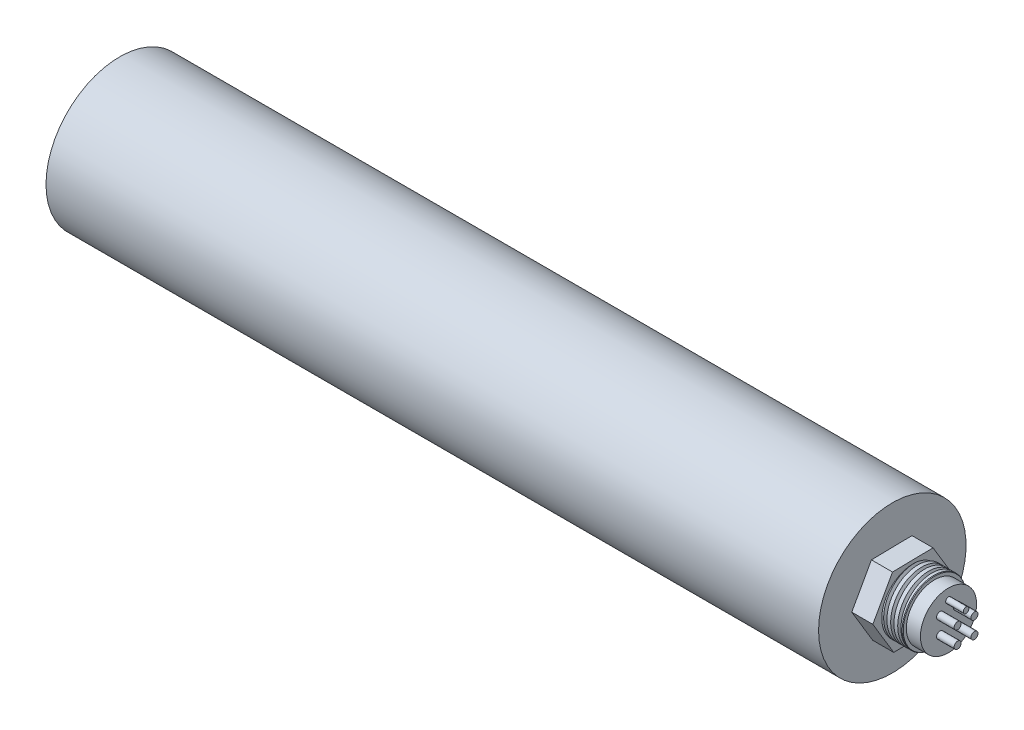
SolidWorks part; units mm, degrees
ref_plane "Front Plane" through (0, 0, 0) normal (0, 0, 1) x (1, 0, 0)
ref_plane "Top Plane" through (0, 0, 0) normal (0, 1, 0) x (1, 0, 0)
ref_plane "Right Plane" through (0, 0, 0) normal (1, 0, 0) x (0, 0, -1)
sketch "Sketch3" plane through (0, 0, 0) normal (1, 0, 0) x (0, 0, -1)
  line L1 (14.6625, 0.2559) -> (7.1096, 12.826)
  line L2 (7.1096, 12.826) -> (-7.5529, 12.5701)
  line L3 (-7.5529, 12.5701) -> (-14.6625, -0.2559)
  line L4 (-14.6625, -0.2559) -> (-7.1096, -12.826)
  line L5 (-7.1096, -12.826) -> (7.5529, -12.5701)
  line L6 (7.5529, -12.5701) -> (14.6625, 0.2559)
  circle A0 centre (0, 0) radius 12.7 construction
extrude "Boss-Extrude1" add sketch "Sketch3" along normal blind 7.62
sketch "Sketch4" plane through (7.62, 0, 0) normal (1, 0, 0) x (0, 0, -1)
  circle A0 centre (0, 0) radius 10.16
extrude "Boss-Extrude2" add sketch "Sketch4" along normal blind 12.7
sketch "Sketch5" plane through (7.62, 0, 0) normal (1, 0, 0) x (0, 0, -1)
  circle A0 centre (0, 0) radius 10.16
extrude "Extrude-Thin1" add sketch "Sketch5" along normal blind 7.62 thin
chamfer "Chamfer2" distance 0.254 angle 30 1 edges at (15.24, 0, -11.43)
sketch "Sketch6" plane through (15.24, 0, 0) normal (1, 0, 0) x (0, 0, -1)
  circle A0 centre (0, 0) radius 11.43
curve "Helix/Spiral1" pitch 2.54 height 7.62 turns 3
sketch "Sketch9" plane through (0, 0, 0) normal (0, 1, 0) x (1, 0, 0)
  line L1 (15.24, 10.414) -> (16.1199, 11.938)
  line L2 (16.1199, 11.938) -> (14.3601, 11.938)
  line L3 (14.3601, 11.938) -> (15.24, 10.414)
  circle A0 centre (15.24, 11.43) radius 0.508 construction
  spline S0 degree 3 poles (15.24, 11.43) (15.1874, 11.43) (15.0811, 10.8349) (14.9225, 8.2926) (14.7637, 4.4879) (14.605, 0) (14.4462, -4.4879) (14.2875, -8.2926) (14.1287, -10.8349) (13.97, -11.7276) (13.8112, -10.8349) (13.6525, -8.2926) (13.4937, -4.4879) (13.335, 0) (13.1762, 4.4879) (13.0175, 8.2926) (12.8587, 10.8349) (12.7, 11.7276) (12.5412, 10.8349) (12.3825, 8.2926) (12.2237, 4.4879) (12.065, 0) (11.9062, -4.4879) (11.7475, -8.2926) (11.5887, -10.8349) (11.43, -11.7276) (11.2712, -10.8349) (11.1125, -8.2926) (10.9537, -4.4879) (10.795, 0) (10.6363, 4.4879) (10.4775, 8.2926) (10.3188, 10.8349) (10.16, 11.7276) (10.0013, 10.8349) (9.8425, 8.2926) (9.6838, 4.4879) (9.525, 0) (9.3663, -4.4879) (9.2075, -8.2926) (9.0488, -10.8349) (8.89, -11.7276) (8.7313, -10.8349) (8.5725, -8.2926) (8.4138, -4.4879) (8.255, 0) (8.0963, 4.4879) (7.9375, 8.2926) (7.7789, 10.8349) (7.6726, 11.43) (7.62, 11.43) knots 0 0 0 0 0.020833 0.041667 0.0625 0.083333 0.104167 0.125 0.145833 0.166667 0.1875 0.208333 0.229167 0.25 0.270833 0.291667 0.3125 0.333333 0.354167 0.375 0.395833 0.416667 0.4375 0.458333 0.479167 0.5 0.520833 0.541667 0.5625 0.583333 0.604167 0.625 0.645833 0.666667 0.6875 0.708333 0.729167 0.75 0.770833 0.791667 0.8125 0.833333 0.854167 0.875 0.895833 0.916667 0.9375 0.958333 0.979167 1 1 1 1 construction
sweep "Cut-Sweep4" cut profiles "Sketch9" path "Helix/Spiral1"
sketch "Sketch10" plane through (0, 0, 0) normal (-1, 0, 0) x (0, 0, 1)
  circle A0 centre (0, 0) radius 26.67
  dimension "D1" = 53.34
extrude "Boss-Extrude3" add sketch "Sketch10" along normal blind 279.4
sketch "Sketch11" plane through (20.32, 0, 0) normal (1, 0, 0) x (0, 0, -1)
  circle A0 centre (-3.048, 3.048) radius 1.27
extrude "Boss-Extrude4" add sketch "Sketch11" along normal blind 6.35
sketch "Sketch12" plane through (20.32, 0, 0) normal (1, 0, 0) x (0, 0, -1)
  circle A0 centre (3.048, 3.048) radius 1.27
extrude "Boss-Extrude5" add sketch "Sketch12" along normal blind 6.35
sketch "Sketch13" plane through (20.32, 0, 0) normal (1, 0, 0) x (0, 0, -1)
  circle A0 centre (3.048, -3.048) radius 1.27
extrude "Boss-Extrude6" add sketch "Sketch13" along normal blind 6.35
sketch "Sketch14" plane through (20.32, 0, 0) normal (1, 0, 0) x (0, 0, -1)
  circle A0 centre (-3.048, -3.048) radius 1.27
extrude "Boss-Extrude7" add sketch "Sketch14" along normal blind 6.35
sketch "Sketch16" plane through (20.32, 0, 0) normal (1, 0, 0) x (0, 0, -1)
  circle A0 centre (0, 6.35) radius 1.016
extrude "Boss-Extrude8" add sketch "Sketch16" along normal blind 6.35
sketch "Sketch17" plane through (0, 0, 0) normal (1, 0, 0) x (0, 0, -1)
  circle A0 centre (0, 0) radius 26.67
extrude "Boss-Extrude9" add sketch "Sketch17" against normal blind 127
